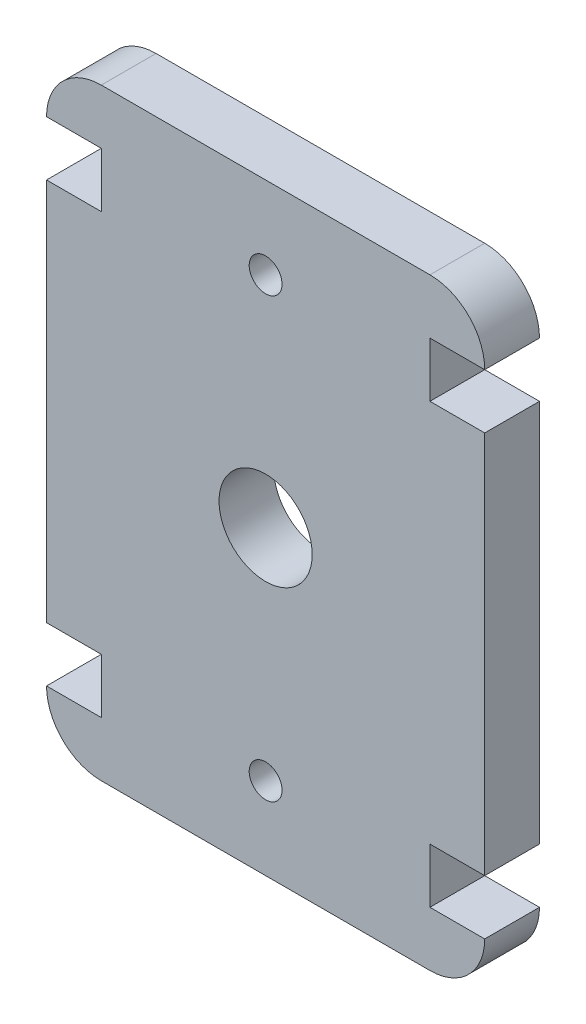
SolidWorks part; units mm, degrees
ref_plane "Plan de face" through (0, 0, 0) normal (0, 0, 1) x (1, 0, 0)
ref_plane "Plan de dessus" through (0, 0, 0) normal (0, 1, 0) x (1, 0, 0)
ref_plane "Plan de droite" through (0, 0, 0) normal (1, 0, 0) x (0, 0, -1)
sketch "Esquisse1" plane through (0, 0, 0) normal (0, 0, 1) x (1, 0, 0)
  line L0 (-20, 0) -> (20, 0)
  line L1 (20, 0) -> (20, 5)
  line L2 (20, 5) -> (15, 5)
  line L3 (15, 5) -> (15, 10)
  line L4 (15, 10) -> (20, 10)
  line L5 (20, 10) -> (20, 45)
  line L6 (20, 45) -> (15, 45)
  line L7 (15, 45) -> (15, 50)
  line L8 (15, 50) -> (20, 50)
  line L9 (20, 50) -> (20, 55)
  line L10 (20, 55) -> (-20, 55)
  line L11 (-20, 55) -> (-20, 50)
  line L12 (-20, 50) -> (-15, 50)
  line L13 (-15, 50) -> (-15, 45)
  line L14 (-15, 45) -> (-20, 45)
  line L15 (-20, 45) -> (-20, 10)
  line L16 (-20, 10) -> (-15, 10)
  line L17 (-15, 10) -> (-15, 5)
  line L18 (-15, 5) -> (-20, 5)
  line L19 (-20, 5) -> (-20, 0)
  line L20 (0, 0) -> (0, 55) construction
  line L21 (-15, 7.5) -> (15, 7.5) construction
  line L22 (15, 47.5) -> (-15, 47.5) construction
  line L23 (-20, 27.5) -> (20, 27.5) construction
  circle A0 centre (0, 47.5) radius 1.5
  circle A1 centre (0, 7.5) radius 1.5
  circle A2 centre (0, 27.5) radius 4.25
  circle A3 centre (-20, 27.5) radius 1.6 construction
  circle A4 centre (20, 27.5) radius 1.6 construction
  dimension "D6" = 3
  dimension "D7" = 3
  dimension "D8" = 8.5
  dimension "D10" = 3.2
  dimension "D1" = 5
  dimension "D2" = 30
  dimension "D3" = 40
  dimension "D4" = 5
  dimension "D5" = 40
  dimension "D9" = 40
  dimension "D11" = 20
extrude "Boss.-Extru.1" add sketch "Esquisse1" along normal blind 5
fillet "Congé1" radius 5 4 edges at (20, 55, 2.5) (20, 0, 2.5) (-20, 0, 2.5) (-20, 55, 2.5)
